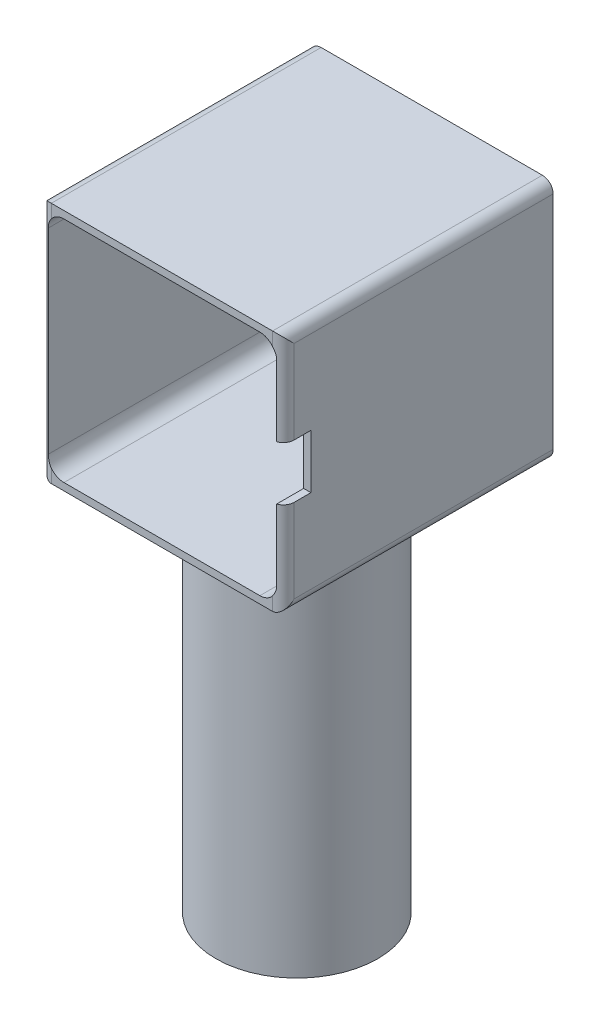
SolidWorks part; units mm, degrees
material "ABS"
ref_plane "Front Plane" through (0, 0, 0) normal (0, 0, 1) x (1, 0, 0)
ref_plane "Top Plane" through (0, 0, 0) normal (0, 1, 0) x (1, 0, 0)
ref_plane "Right Plane" through (0, 0, 0) normal (1, 0, 0) x (0, 0, -1)
sketch "Sketch1" plane through (0, 0, 0) normal (0, 0, 1) x (1, 0, 0)
  line L1 (-22.5, 22.5) -> (22.5, 22.5)
  line L2 (-22.5, 22.5) -> (-22.5, -22.5)
  line L3 (-22.5, -22.5) -> (22.5, -22.5)
  line L4 (22.5, 22.5) -> (22.5, -22.5)
  line L5 (-22.5, 22.5) -> (22.5, -22.5) construction
  line L6 (-22.5, -22.5) -> (22.5, 22.5) construction
  point P0 (0, 0)
  dimension "D1" = 45
  dimension "D2" = 45
extrude "Boss-Extrude1" add sketch "Sketch1" along normal blind 50
sketch "Sketch2" plane through (0, 0, 50) normal (0, 0, 1) x (1, 0, 0)
  line L1 (-21.15, -21.15) -> (21.15, -21.15)
  line L2 (-21.15, -21.15) -> (-21.15, 21.15)
  line L3 (-21.15, 21.15) -> (21.15, 21.15)
  line L4 (21.15, -21.15) -> (21.15, 21.15)
  line L5 (-21.15, -21.15) -> (21.15, 21.15) construction
  line L6 (-21.15, 21.15) -> (21.15, -21.15) construction
  point P0 (0, 0)
  dimension "D1" = 42.3
  dimension "D2" = 42.3
extrude "Cut-Extrude1" cut sketch "Sketch2" against normal blind 46
sketch "Sketch3" plane through (0, 0, 4) normal (0, 0, 1) x (1, 0, 0)
  line L0 (-15.4998, 15.4998) -> (0, 0) construction
  line L1 (0, 0) -> (0, 21.15) construction
  line L2 (21.15, 21.15) -> (-21.15, 21.15) construction
  circle A0 centre (-15.4998, 15.4998) radius 1.5
  circle A1 centre (15.4998, 15.4998) radius 1.5
  circle A2 centre (15.4998, -15.4998) radius 1.5
  circle A3 centre (-15.4998, -15.4998) radius 1.5
  circle A4 centre (0, 0) radius 2.75
  point P15 (0, 0)
  dimension "D1" = 3
  dimension "D5" = 5.5
  dimension "D2" = 21.92
  dimension "D3" = 45
  dimension "D4" = 4
extrude "Cut-Extrude2" cut sketch "Sketch3" against normal through all both and the other way through all
sketch "Sketch4" plane through (0, -22.5, 0) normal (0, -1, 0) x (1, 0, 0)
  line L0 (0, 50) -> (0, 0) construction
  line L1 (-22.5, 50) -> (22.5, 50) construction
  circle A0 centre (0, 25) radius 15
  dimension "D1" = 30
  dimension "D2" = 25
extrude "Boss-Extrude2" add sketch "Sketch4" along normal blind 71
fillet "Fillet1" radius 2 6 edges at (-22.5, 0, 50) (22.5, 0, 50) (22.5, -22.5, 25) (-22.5, -22.5, 25) (-22.5, 22.5, 25) (22.5, 22.5, 25)
fillet "Fillet2" radius 5 1 edges at (0, -22.5, 10)
fillet "Fillet3" radius 3 4 edges at (-21.15, -21.15, 26.9457) (21.15, 21.15, 26.9457) (-21.15, 21.15, 26.9457) (21.15, -21.15, 26.9457)
ref_plane "Plane1" through (0, -27.5, 0) normal (0, -1, 0) x (-1, 0, 0)
sketch "Sketch6" plane through (0, -27.5, 0) normal (0, -1, 0) x (-1, 0, 0)
  line L0 (0, -25) -> (0, -49.5) construction
  dimension "D1" = 24.5
sketch "Sketch7" plane through (22.5, 0, 0) normal (1, 0, 0) x (0, 0, -1)
  line L0 (-49.8914, -18.15) -> (-49.8914, 18.15) construction
  line L1 (-44.8914, 5) -> (-49.8914, 5)
  line L2 (-44.8914, 5) -> (-44.8914, -5)
  line L3 (-44.8914, -5) -> (-49.8914, -5)
  line L4 (-49.8914, 5) -> (-49.8914, -5)
  point P6 (-49.8914, 0)
  dimension "D1" = 10
  dimension "D2" = 5
  dimension "D3" = 0
extrude "Cut-Extrude3" cut sketch "Sketch7" against normal blind 10
